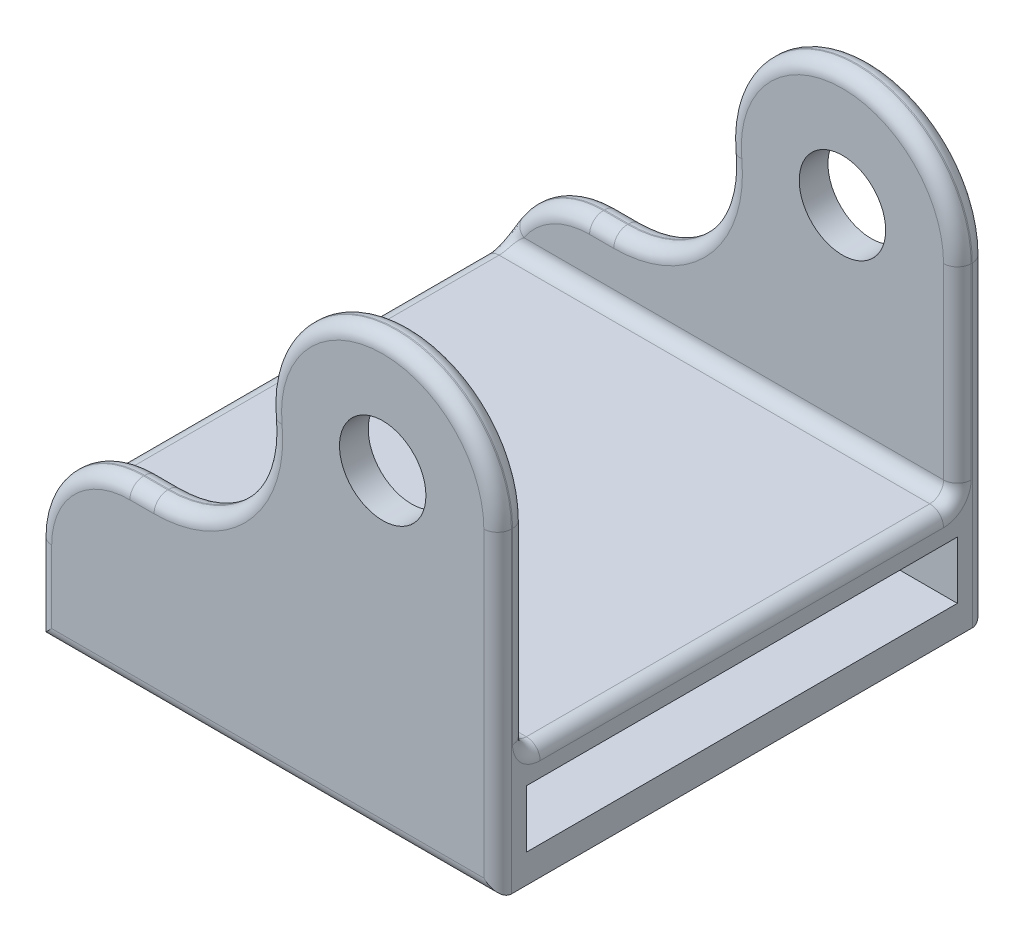
SolidWorks part; units mm, degrees
material "Chrome Stainless Steel"
ref_plane "Front" through (0, 0, 0) normal (0, 0, 1) x (1, 0, 0)
ref_plane "Top" through (0, 0, 0) normal (0, 1, 0) x (1, 0, 0)
ref_plane "Right" through (0, 0, 0) normal (1, 0, 0) x (0, 0, -1)
sketch "Sketch1" plane through (0, 0, 0) normal (0, 0, 1) x (1, 0, 0)
  line L0 (0, 0) -> (-25.4, 0)
  line L1 (0, 0) -> (0, 12.7)
  line L2 (-18.9863, 5.08) -> (-20.32, 5.08)
  arc A0 (0, 12.7) -> (-12.6682, 12.065) centre (-6.35, 12.7) ccw
  arc A1 (-12.6682, 12.065) -> (-18.9863, 5.08) centre (-18.9863, 11.43) cw
  arc A2 (-20.32, 5.08) -> (-25.4, 0) centre (-20.32, 0) ccw
  dimension "D2" = 12.7
  dimension "D3" = 6.35
  dimension "D4" = 5.08
  dimension "D5" = 6.35
  dimension "D1" = 25.4
extrude "Extrude1" add sketch "Sketch1" along normal mid plane 26.9875
shell "Shell1" thickness 1.5875 removed face at (0, 6.35, 0) removed face at (-6.501, 15.7123, 0) removed face at (-15.0522, 7.8714, 0) removed face at (-23.3861, 3.0661, 0) removed face at (-19.6532, 5.08, 0)
sketch "Sketch2" plane through (0, 0, 13.4937) normal (0, 0, 1) x (1, 0, 0)
  circle A0 centre (-6.35, 12.7) radius 2.3876
  dimension "D1" = 4.7752
extrude "Cut-Extrude1" cut sketch "Sketch2" against normal through all
sketch "Sketch3" plane through (0, 0, 0) normal (0, -1, 0) x (1, 0, 0)
  line L4 (-25.4, -13.4937) -> (0, -13.4937)
  line L5 (0, -13.4937) -> (0, 13.4937)
  line L6 (0, 13.4937) -> (-25.4, 13.4937)
  line L7 (-25.4, 13.4937) -> (-25.4, -13.4937)
  line L8 (-25.4, -13.4937) -> (0, -13.4937)
  line L9 (0, -13.4937) -> (0, 13.4937)
  line L10 (0, 13.4937) -> (-25.4, 13.4937)
  line L11 (-25.4, 13.4937) -> (-25.4, -13.4937)
  dimension "D1" = 0
extrude "Extrude2" add sketch "Sketch3" along normal blind 4.7625
sketch "Sketch4" plane through (0, 0, 0) normal (1, 0, 0) x (0, 0, -1)
  line L0 (11.9062, 1.5875) -> (11.9062, 12.7) construction
  line L1 (-11.9062, 0) -> (11.9062, 0)
  line L2 (-11.9062, 0) -> (-11.9062, -3.175)
  line L3 (-11.9062, -3.175) -> (11.9062, -3.175)
  line L4 (11.9062, 0) -> (11.9062, -3.175)
  line L5 (-11.9062, 1.5875) -> (-11.9062, 12.7) construction
  line L7 (13.4937, -4.7625) -> (-13.4937, -4.7625) construction
  dimension "D1" = 3.175
  dimension "D2" = 1.5875
extrude "Cut-Extrude2" cut sketch "Sketch4" against normal through all
fillet "Fillet1" radius 0.762 28 edges at (0, 7.1437, 11.9062) (-6.6679, 19.042, 11.9062) (-14.2771, 7.1703, 11.9062) (-19.6532, 5.08, 11.9062) (0, 7.1437, -11.9062) (-6.6679, 19.042, -11.9062) (-14.2771, 7.1703, -11.9062) (-19.6532, 5.08, -11.9062) (0, 3.9688, 13.4937) (-6.6679, 19.042, 13.4937) (-14.2771, 7.1703, 13.4937) (-19.6532, 5.08, 13.4937) (-25.4, -2.3813, 13.4937) (0, 3.9688, -13.4937) (-6.6679, 19.042, -13.4937) (-14.2771, 7.1703, -13.4937) (-19.6532, 5.08, -13.4937) (-23.9121, 3.5921, -13.4937) (-12.7, -4.7625, -13.4937) (-12.7, -4.7625, 13.4937) (-12.5728, 1.5875, -11.9062) (-12.5728, 1.5875, 11.9062) (0, 1.5875, 0) (-25.1456, 1.5875, 0) (-23.2984, 4.1153, 11.9062) (-23.2984, 4.1153, -11.9062) (-23.9121, 3.5921, 13.4937) (-25.4, -2.3813, -13.4937)
